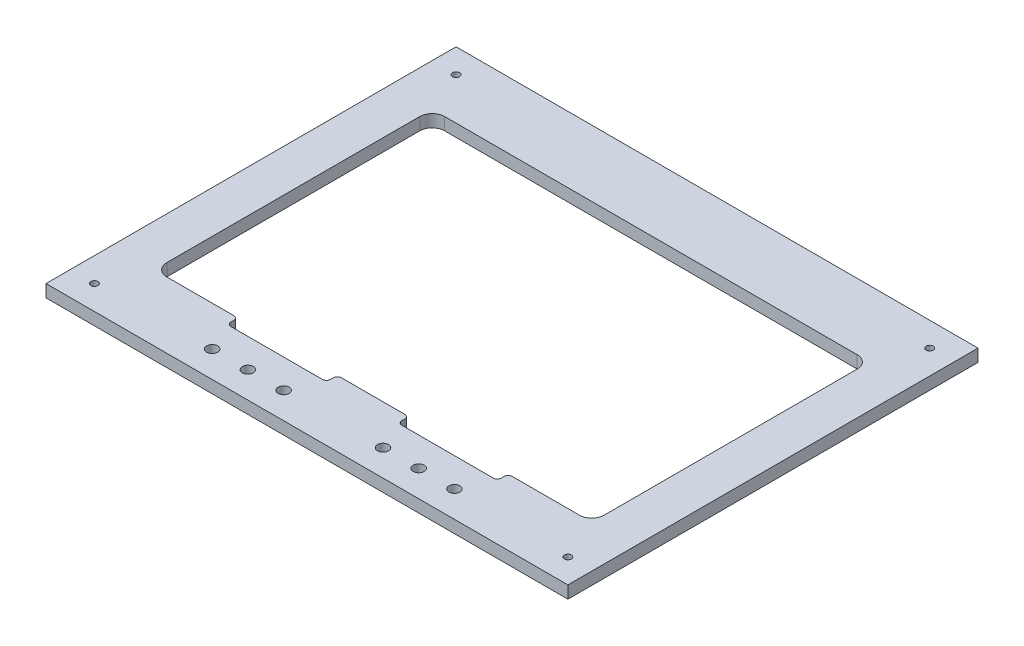
SolidWorks part; units mm, degrees
material "Acrylic (Medium-high impact)"
ref_plane "Front Plane" through (0, 0, 0) normal (0, 0, 1) x (1, 0, 0)
ref_plane "Top Plane" through (0, 0, 0) normal (0, 1, 0) x (1, 0, 0)
ref_plane "Right Plane" through (0, 0, 0) normal (1, 0, 0) x (0, 0, -1)
sketch "Sketch1" plane through (0, 0, 0) normal (0, 1, 0) x (1, 0, 0)
  line L1 (-133.35, 104.775) -> (133.35, 104.775)
  line L2 (-133.35, 104.775) -> (-133.35, -104.775)
  line L3 (-133.35, -104.775) -> (133.35, -104.775)
  line L4 (133.35, 104.775) -> (133.35, -104.775)
  line L5 (-133.35, 104.775) -> (133.35, -104.775) construction
  line L6 (-133.35, -104.775) -> (133.35, 104.775) construction
  point P0 (0, 0)
  dimension "D1" = 209.55
  dimension "D2" = 266.7
extrude "Boss-Extrude1" add sketch "Sketch1" along normal blind 6.35
hole_wizard "M3 Clearance Hole1" positions "Sketch2" profile "Sketch3" hole size "M3" standard "ANSI Metric" end condition through all
sketch "Sketch2" plane through (0, 6.35, 0) normal (0, 1, 0) x (1, 0, 0)
  line L0 (-133.35, -104.775) -> (133.35, -104.775) construction
  line L1 (133.35, -104.775) -> (133.35, 104.775) construction
  line L2 (133.35, 104.775) -> (-133.35, 104.775) construction
  line L3 (-133.35, 104.775) -> (-133.35, -104.775) construction
  point P0 (121.0056, -92.4306)
  point P2 (-121.0056, -92.4306)
  point P4 (-121.0056, 92.4306)
  point P6 (121.0056, 92.4306)
  dimension "D1" = 12.3444
  dimension "D2" = 12.3444
  dimension "D3" = 12.3444
  dimension "D4" = 12.3444
sketch "Sketch3" plane through (121.0056, 6.35, 92.4306) normal (1, 0, 0) x (0, 0, 1)
  line L0 (0, 0) -> (0, 6.35)
  line L1 (0, 6.35) -> (1.8, 6.35)
  line L2 (1.8, 6.35) -> (1.8, 0)
  line L5 (1.8, 0) -> (0, 0)
  line L11 (0, -6.35) -> (0, 107.95) construction
  dimension "Thru Hole Dia." = 3.6
  dimension "Thru Hole Depth" = 6.35
sketch "Sketch4" plane through (0, 6.35, 0) normal (0, 1, 0) x (1, 0, 0)
  line L0 (-133.35, 104.775) -> (-133.35, -104.775) construction
  line L1 (111.76, -70.993) -> (-111.76, -70.993)
  line L2 (111.76, -70.993) -> (111.76, 70.993)
  line L3 (111.76, 70.993) -> (-111.76, 70.993)
  line L4 (-111.76, -70.993) -> (-111.76, 70.993)
  line L5 (111.76, -70.993) -> (-111.76, 70.993) construction
  line L6 (111.76, 70.993) -> (-111.76, -70.993) construction
  line L7 (133.35, 104.775) -> (-133.35, 104.775) construction
  point P0 (0, 0)
  dimension "D1" = 21.59
  dimension "D2" = 33.782
extrude "Cut-Extrude1" cut sketch "Sketch4" against normal through all
hole_wizard "#10 Clearance Hole1" positions "Sketch5" profile "Sketch6" hole size "#10" standard "ANSI Inch" end condition through all
sketch "Sketch5" plane through (0, 6.35, 0) normal (0, 1, 0) x (1, 0, 0)
  line L0 (-61.9125, -91.313) -> (-25.4, -91.313) construction
  line L2 (25.4, -91.313) -> (61.9125, -91.313) construction
  line L4 (-25.4, -91.313) -> (25.4, -91.313) construction
  line L5 (-111.76, -70.993) -> (111.76, -70.993) construction
  point P0 (-61.9125, -91.313)
  point P2 (-43.6562, -91.313)
  point P4 (-25.4, -91.313)
  point P6 (25.4, -91.313)
  point P8 (43.6562, -91.313)
  point P10 (61.9125, -91.313)
  point P22 (43.6562, -91.313)
  point P23 (-43.6562, -91.313)
  point P29 (0, -91.313)
  dimension "D1" = 36.5125
  dimension "D2" = 36.5125
  dimension "D3" = 50.8
  dimension "D4" = 20.32
sketch "Sketch6" plane through (-61.9125, 6.35, 91.313) normal (1, 0, 0) x (0, 0, 1)
  line L0 (0, 0) -> (0, 6.35)
  line L1 (0, 6.35) -> (2.8067, 6.35)
  line L2 (2.8067, 6.35) -> (2.8067, 0)
  line L5 (2.8067, 0) -> (0, 0)
  line L11 (0, -6.35) -> (0, 107.95) construction
  dimension "Thru Hole Dia." = 5.6134
  dimension "Thru Hole Depth" = 6.35
sketch "Sketch7" plane through (0, 6.35, 0) normal (0, 1, 0) x (1, 0, 0)
  line L0 (-111.76, -70.993) -> (111.76, -70.993) construction
  line L1 (-69.0563, -76.581) -> (-18.2563, -76.581)
  line L2 (-69.0563, -76.581) -> (-69.0563, -70.993)
  line L3 (-69.0563, -70.993) -> (-18.2563, -70.993)
  line L4 (-18.2563, -76.581) -> (-18.2563, -70.993)
  line L5 (-69.0563, -76.581) -> (-18.2563, -70.993) construction
  line L6 (-69.0563, -70.993) -> (-18.2563, -76.581) construction
  line L7 (-43.6562, -73.787) -> (-43.6562, -91.313) construction
  line L8 (18.2562, -76.581) -> (69.0562, -76.581)
  line L9 (18.2562, -76.581) -> (18.2562, -70.993)
  line L10 (18.2562, -70.993) -> (69.0562, -70.993)
  line L11 (69.0562, -76.581) -> (69.0562, -70.993)
  line L12 (18.2562, -76.581) -> (69.0562, -70.993) construction
  line L13 (18.2562, -70.993) -> (69.0562, -76.581) construction
  line L14 (43.6562, -73.787) -> (43.6562, -91.313) construction
  point P0 (-43.6563, -73.787)
  point P7 (43.6562, -73.787)
  dimension "D3" = 50.8
  dimension "D4" = 5.588
extrude "Cut-Extrude2" cut sketch "Sketch7" against normal through all
fillet "Fillet1" radius 6.35 4 edges at (111.76, 3.175, -70.993) (111.76, 3.175, 70.993) (-111.76, 3.175, 70.993) (-111.76, 3.175, -70.993)
fillet "Fillet2" radius 2.032 8 edges at (69.0562, 3.175, 70.993) (69.0562, 3.175, 76.581) (18.2562, 3.175, 76.581) (18.2562, 3.175, 70.993) (-18.2563, 3.175, 70.993) (-18.2563, 3.175, 76.581) (-69.0562, 3.175, 70.993) (-69.0563, 3.175, 76.581)
